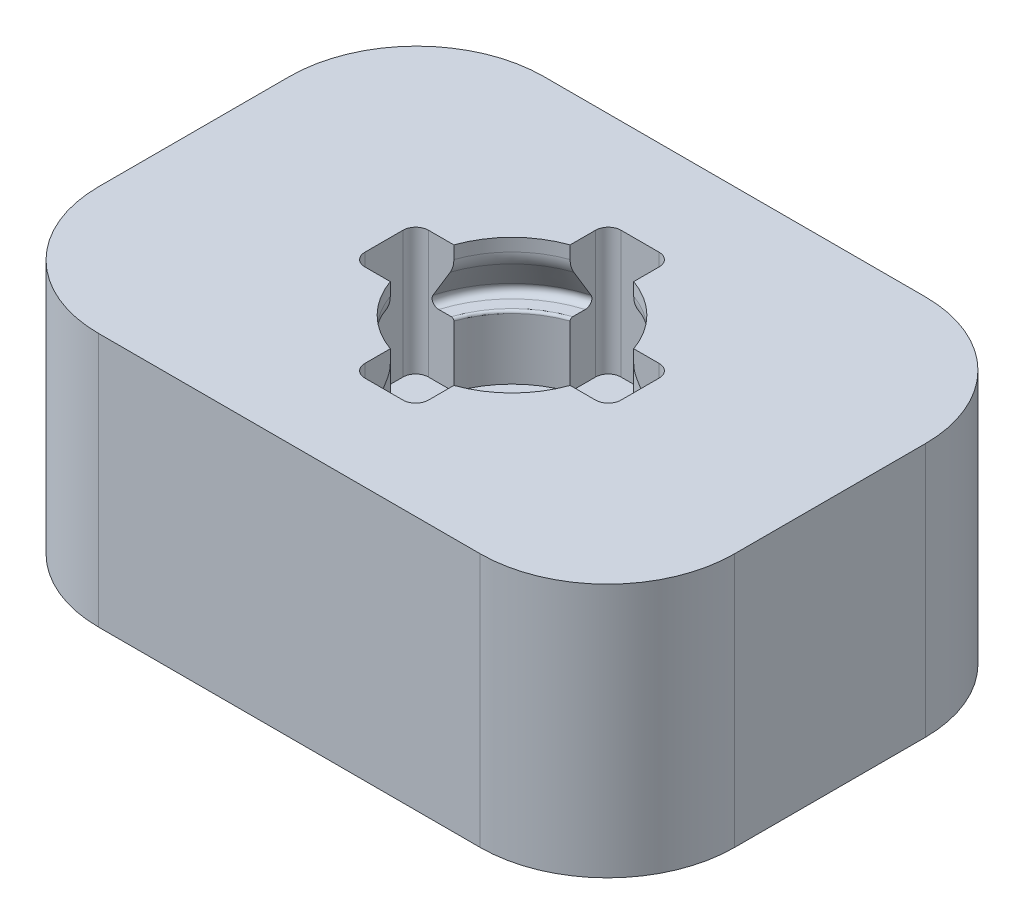
SolidWorks part; units mm, degrees
ref_plane "Alzado" through (0, 0, 0) normal (0, 0, 1) x (1, 0, 0)
ref_plane "Planta" through (0, 0, 0) normal (0, 1, 0) x (1, 0, 0)
ref_plane "Vista lateral" through (0, 0, 0) normal (1, 0, 0) x (0, 0, -1)
sketch "Croquis1" plane through (0, 0, 0) normal (0, 1, 0) x (1, 0, 0)
  line L1 (-25, 17.5) -> (25, 17.5)
  line L2 (-25, 17.5) -> (-25, -17.5)
  line L3 (-25, -17.5) -> (25, -17.5)
  line L4 (25, 17.5) -> (25, -17.5)
  line L5 (-25, 17.5) -> (25, -17.5) construction
  line L6 (-25, -17.5) -> (25, 17.5) construction
  point P0 (0, 0)
  dimension "D1" = 50
  dimension "D2" = 35
extrude "Saliente-Extruir1" add sketch "Croquis1" along normal blind 20
fillet "Redondeo1" radius 10 4 edges at (-25, 10, -17.5) (25, 10, -17.5) (25, 10, 17.5) (-25, 10, 17.5)
shell "Vaciado2" thickness 2 removed face at (0, 0, 0)
sketch "Croquis2" plane through (0, 18, 0) normal (0, -1, 0) x (1, 0, 0)
  circle A0 centre (0, 0) radius 7.5
  dimension "D1" = 15
extrude "Cortar-Extruir1" cut sketch "Croquis2" against normal up to next
sketch "Croquis4" plane through (0, 0, 0) normal (0, 0, 1) x (1, 0, 0)
  line L0 (0, 0) -> (0, 65) construction
  line L1 (-15, 20) -> (15, 20) construction
  line L2 (12.5, 20) -> (12.5, 10)
  line L4 (12.5, 10) -> (7.5, 10)
  line L6 (7.5, 20) -> (12.5, 20)
  line L7 (7.5, 10) -> (7.5, 20)
  dimension "D1" = 25
  dimension "D2" = 10
  dimension "D3" = 45
revolve "Revolución1" add sketch "Croquis4" angle 360 about L0
sketch "Croquis6" plane through (0, 0, 0) normal (0, 0, 1) x (1, 0, 0)
  line L0 (7.6999, 15.007) -> (8.6299, 15.007)
  line L1 (9.0629, 15.757) -> (7.7679, 18)
  line L2 (7.5, 20) -> (7.5, 14.8018) construction
  line L3 (7.5, 19) -> (7.5, 14.8018)
  line L4 (7.5, 20) -> (-7.5, 20) construction
  line L5 (0, 0) -> (0, 20) construction
  line L6 (15, 0) -> (-15, 0) construction
  arc A0 (8.6299, 15.007) -> (9.0629, 15.757) centre (8.6299, 15.507) ccw
  arc A1 (7.7679, 18) -> (7.5, 19) centre (9.5, 19) cw
  arc A2 (7.5, 14.8018) -> (7.6999, 15.007) centre (7.6999, 14.807) cw
  dimension "D2" = 0.5
  dimension "D3" = 2
  dimension "D4" = 0.2
  dimension "D1" = 60
  dimension "D5" = 0.93
  dimension "D6" = 2.59
  dimension "D7" = 0.7051
  dimension "D8" = 1
revolve "Cortar-Revolución1" cut sketch "Croquis6" angle 360 about L5 region at (8.1069, 16.2236, 0)
fillet "Redondeo4" radius 1 1 edges at (0, 18, 12.5)
sketch "Croquis5" plane through (0, 10, 0) normal (0, -1, 0) x (1, 0, 0)
  line L0 (0, -12.5) -> (0, 12.5) construction
  line L1 (12.5, 0) -> (-12.5, 0) construction
  line L2 (9.0711, 2.5) -> (7.0711, 2.5)
  line L3 (-1.5, 10.0711) -> (1.5, 10.0711)
  line L4 (-2.5, 9.0711) -> (-2.5, 7.0711)
  line L5 (-2.5, 7.0711) -> (2.5, 7.0711)
  line L6 (2.5, 9.0711) -> (2.5, 7.0711)
  line L7 (10.0711, 1.5) -> (10.0711, -1.5)
  line L8 (9.0711, -2.5) -> (7.0711, -2.5)
  line L9 (7.0711, 2.5) -> (7.0711, -2.5)
  line L10 (2.5, -9.0711) -> (2.5, -7.0711)
  line L11 (1.5, -10.0711) -> (-1.5, -10.0711)
  line L12 (-2.5, -9.0711) -> (-2.5, -7.0711)
  line L13 (2.5, -7.0711) -> (-2.5, -7.0711)
  line L14 (-9.0711, -2.5) -> (-7.0711, -2.5)
  line L15 (-10.0711, -1.5) -> (-10.0711, 1.5)
  line L16 (-9.0711, 2.5) -> (-7.0711, 2.5)
  line L17 (-7.0711, -2.5) -> (-7.0711, 2.5)
  circle A1 centre (0, 0) radius 7.5 construction
  arc A2 (1.5, 10.0711) -> (2.5, 9.0711) centre (1.5, 9.0711) cw
  arc A3 (-1.5, 10.0711) -> (-2.5, 9.0711) centre (-1.5, 9.0711) ccw
  arc A4 (10.0711, 1.5) -> (9.0711, 2.5) centre (9.0711, 1.5) ccw
  arc A5 (10.0711, -1.5) -> (9.0711, -2.5) centre (9.0711, -1.5) cw
  arc A6 (1.5, -10.0711) -> (2.5, -9.0711) centre (1.5, -9.0711) ccw
  arc A7 (-1.5, -10.0711) -> (-2.5, -9.0711) centre (-1.5, -9.0711) cw
  arc A8 (-10.0711, -1.5) -> (-9.0711, -2.5) centre (-9.0711, -1.5) ccw
  arc A9 (-10.0711, 1.5) -> (-9.0711, 2.5) centre (-9.0711, 1.5) cw
  circle A10 centre (0, 0) radius 12.5 construction
  circle A11 centre (0, 0) radius 12.5 construction
  point P7 (0, 0)
  point P11 (0, 0)
  point P19 (0, 7.0711)
  point P22 (2.5, 10.0711)
  point P50 (0, 0)
  dimension "D3" = 1
  dimension "D1" = 5
  dimension "D2" = 3
  dimension "D4" = 4
extrude "Cortar-Extruir2" cut sketch "Croquis5" against normal up to surface (10 mm away) up to face at (0, 20, 0)
sketch "Croquis7" plane through (0, 10, 0) normal (0, -1, 0) x (1, 0, 0)
  circle A0 centre (0, 0) radius 12.5 construction
  circle A1 centre (0, 0) radius 12.5
extrude "Saliente-Extruir3" add sketch "Croquis7" along normal blind 3
